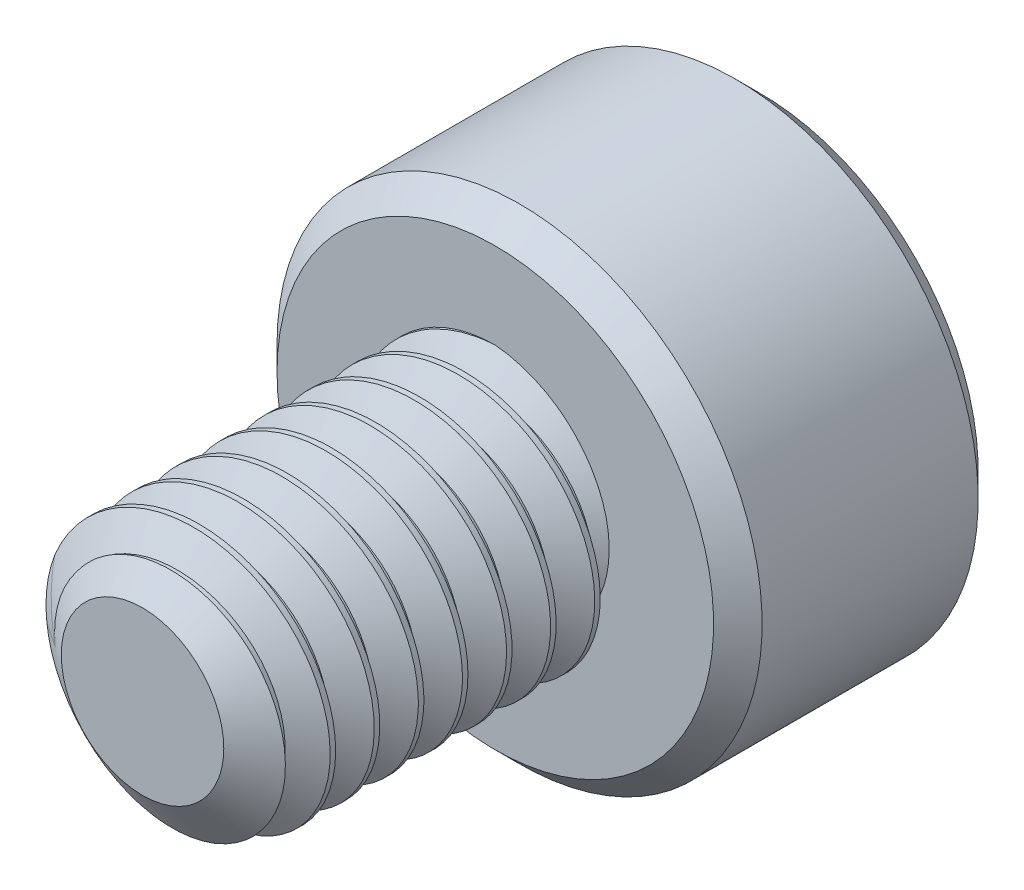
SolidWorks part; units mm, degrees
other "DetailItem1"
ref_plane "Front Plane" through (0, 0, 0) normal (0, 0, 1) x (1, 0, 0)
ref_plane "Top Plane" through (0, 0, 0) normal (0, 1, 0) x (1, 0, 0)
ref_plane "Right Plane" through (0, 0, 0) normal (1, 0, 0) x (0, 0, -1)
sketch "Sketch1" plane through (0, 0, 0) normal (0, 0, 1) x (1, 0, 0)
  circle A0 centre (0, 0) radius 1.5
  dimension "OD" = 3
extrude "Extrude1" add sketch "Sketch1" against normal blind 4
sketch "Sketch2" plane through (0, 0, 0) normal (0, 0, 1) x (1, 0, 0)
  circle A0 centre (0, 0) radius 1.5 construction
  circle A1 centre (0, 0) radius 1.5
curve "Helix/Spiral1" pitch 0.5 height 4.5 radius 1.5 centre (0, 0, 0) axis (0, 0, -1) start towards (0, 1, 0) parameters "pitch"=0.5
sketch "Sketch3" plane through (0, 0, 0) normal (1, 0, 0) x (0, 0, -1)
  line L0 (-0.4375, 1.5) -> (-0.25, 1.1752)
  line L1 (-0.25, 1.1752) -> (-0.1875, 1.1752)
  line L2 (-0.1875, 1.1752) -> (0, 1.5)
  line L3 (-0.4375, 1.5) -> (0, 1.5)
  line L4 (-0.2187, 1.5) -> (-0.2188, 1.1752) construction
  line L5 (-0.3438, 1.3376) -> (-0.0938, 1.3376) construction
  line L6 (0, 1.5) -> (0, -1.5) construction
  dimension "D1" = 0.0625
  dimension "D2" = 0.25
  dimension "D3" = 60
sweep "Cut-Sweep1" cut profiles "Sketch3" path "Helix/Spiral1"
sketch "Sketch4" plane through (0, 0, 0) normal (1, 0, 0) x (0, 0, -1)
  line L0 (0.4053, 1.5) -> (0, 0.9212)
  line L1 (0, 0.9212) -> (0, 1.5)
  line L2 (0.4053, 1.5) -> (0, 1.5)
  line L3 (-0.4375, 1.5) -> (0, 1.5) construction
  line L4 (0, 0) -> (7.0209, 0) construction
  dimension "D1" = 55
  dimension "D2" = 0.254
revolve "Cut-Revolve1" cut sketch "Sketch4" angle 360 about L4
sketch "Sketch6" plane through (0, 0, -4) normal (0, 0, -1) x (-1, 0, 0)
  circle A0 centre (0, 0) radius 2.75
  dimension "head dia" = 5.5
extrude "Extrude2" add sketch "Sketch6" along normal blind 3
sketch "Sketch7" plane through (0, 0, -7) normal (0, 0, -1) x (-1, 0, 0)
  line L1 (0, 1.4434) -> (-1.25, 0.7217)
  line L2 (-1.25, 0.7217) -> (-1.25, -0.7217)
  line L3 (-1.25, -0.7217) -> (0, -1.4434)
  line L4 (0, -1.4434) -> (1.25, -0.7217)
  line L5 (1.25, -0.7217) -> (1.25, 0.7217)
  line L6 (1.25, 0.7217) -> (0, 1.4434)
  circle A0 centre (0, 0) radius 1.25 construction
  dimension "hex dia" = 2.5
extrude "Cut-Extrude1" cut sketch "Sketch7" against normal blind 1.875
sketch "Sketch8" plane through (0, 0, -7) normal (0, 0, -1) x (-1, 0, 0)
  circle A0 centre (0, 0) radius 1.4434
extrude "Cut-Extrude2" cut sketch "Sketch8" against normal through all draft 45
chamfer "Chamfer1" distance 0.275 angle 45 2 edges at (-2.75, 0, -7) (-2.75, 0, -4)
sketch "Sketch10" plane through (0, 0, -4) normal (0, 0, 1) x (1, 0, 0)
  circle A1 centre (0, 0) radius 1.5
  circle A2 centre (0, 0) radius 1.5
  dimension "D1" = 0
ref_plane "Plane1" through (0, 0, 0) normal (0, 0, 1) x (1, 0, 0)
extrude "partial thread" [suppressed] add sketch "Sketch10" along normal up to surface (4 mm away) separate body up to plane "Plane1"
chamfer "Chamfer2" [suppressed] distance 0.06 angle 45
combine bodies "Combine1" [suppressed] operation type add bodies to combine 107 108
sketch "Sketch9" plane through (0, 0, 0) normal (1, 0, 0) x (0, 0, -1)
  line L0 (0, 1.5) -> (0, -1.5) construction
  line L1 (1.25, 1.5) -> (1.25, -1.5) construction
  dimension "D1" = 1.25
equation "\"D3@Helix/Spiral1\" = \"screw length@Extrude1\"+\"pitch@Helix/Spiral1\""
equation "\"D1@Sketch3\" = \"pitch@Helix/Spiral1\"*.125"
equation "\"D2@Sketch3\" = \"pitch@Helix/Spiral1\"*.5"
equation "\"D1@Cut-Extrude1\" = \"hex dia@Sketch7\"*.75"
equation "\"D1@Chamfer1\" = \"head dia@Sketch6\"*.05"
equation "\"D1@Sketch9\" = \"pitch@Helix/Spiral1\"*2.5"
equation "\"D1@Chamfer2\"=\"OD@Sketch1\"*.02"
